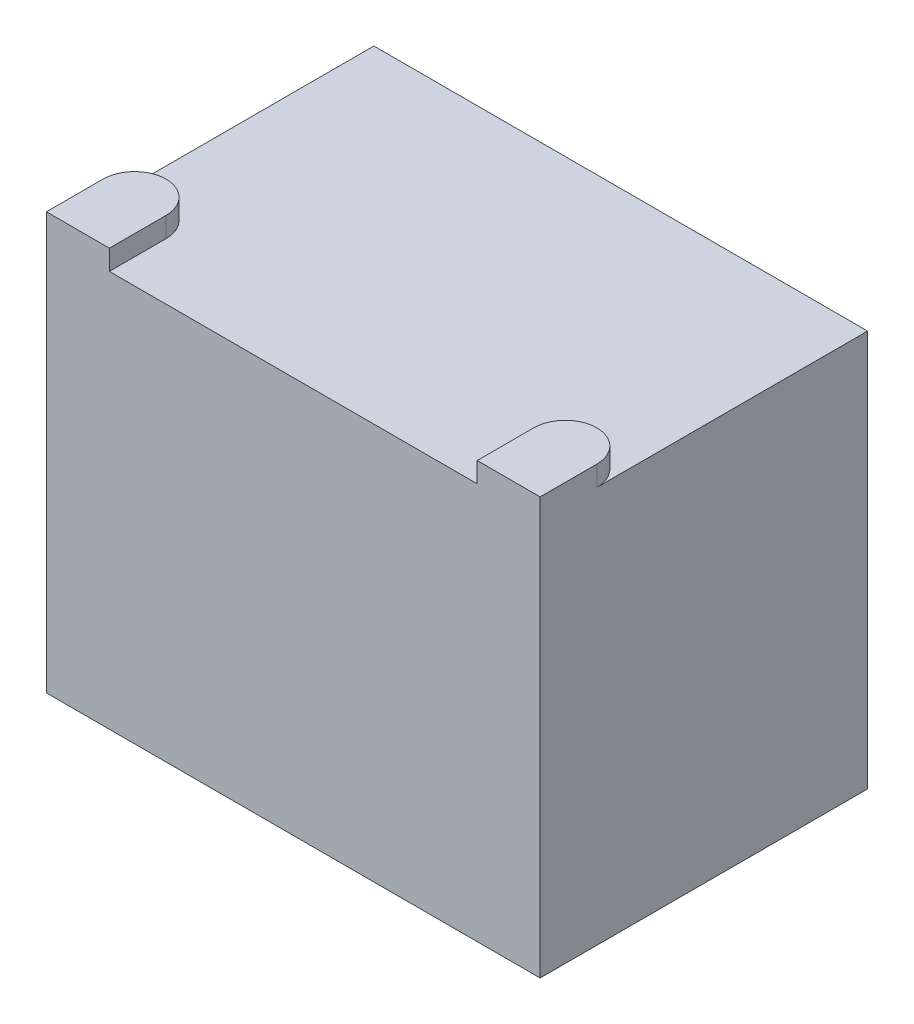
SolidWorks part; units mm, degrees
ref_plane "前视基准面" through (0, 0, 0) normal (0, 0, 1) x (1, 0, 0)
ref_plane "上视基准面" through (0, 0, 0) normal (0, 1, 0) x (1, 0, 0)
ref_plane "右视基准面" through (0, 0, 0) normal (1, 0, 0) x (0, 0, -1)
sketch "草图1" plane through (0, 0, 0) normal (0, 1, 0) x (1, 0, 0)
  line L1 (-98.044, 65.024) -> (98.044, 65.024)
  line L2 (-98.044, 65.024) -> (-98.044, -65.024)
  line L3 (-98.044, -65.024) -> (98.044, -65.024)
  line L4 (98.044, 65.024) -> (98.044, -65.024)
  line L5 (-98.044, 65.024) -> (98.044, -65.024) construction
  line L6 (-98.044, -65.024) -> (98.044, 65.024) construction
  point P0 (0, 0)
  dimension "D1" = 196.088
  dimension "D2" = 130.048
extrude "凸台-拉伸1" add sketch "草图1" along normal blind 157.48
sketch "草图3" plane through (0, 157.48, 0) normal (0, 1, 0) x (1, 0, 0)
  line L1 (-98.044, -65.024) -> (-73.044, -65.024)
  line L2 (-98.044, -65.024) -> (-98.044, -30.024)
  line L3 (-98.044, -30.024) -> (-73.044, -30.024)
  line L4 (-73.044, -65.024) -> (-73.044, -30.024)
  line L5 (-85.544, -30.024) -> (-85.544, -65.024) construction
  line L6 (-98.044, -47.524) -> (-73.044, -47.524) construction
  line L7 (98.044, -65.024) -> (73.044, -65.024)
  line L8 (98.044, -65.024) -> (98.044, -30.024)
  line L9 (98.044, -30.024) -> (73.044, -30.024)
  line L10 (73.044, -65.024) -> (73.044, -30.024)
  line L11 (85.544, -30.024) -> (85.544, -65.024) construction
  line L12 (98.044, -47.524) -> (73.044, -47.524) construction
  point P44 (-85.544, -47.524)
  point P66 (85.544, -47.524)
  dimension "D1" = 25
  dimension "D2" = 35
  dimension "D3" = 35
  dimension "D4" = 25
extrude "凸台-拉伸2" add sketch "草图3" along normal blind 8
fillet "圆角2" radius 12.5 4 edges at (73.044, 161.48, 30.024) (98.044, 161.48, 30.024) (-98.044, 161.48, 30.024) (-73.044, 161.48, 30.024)
